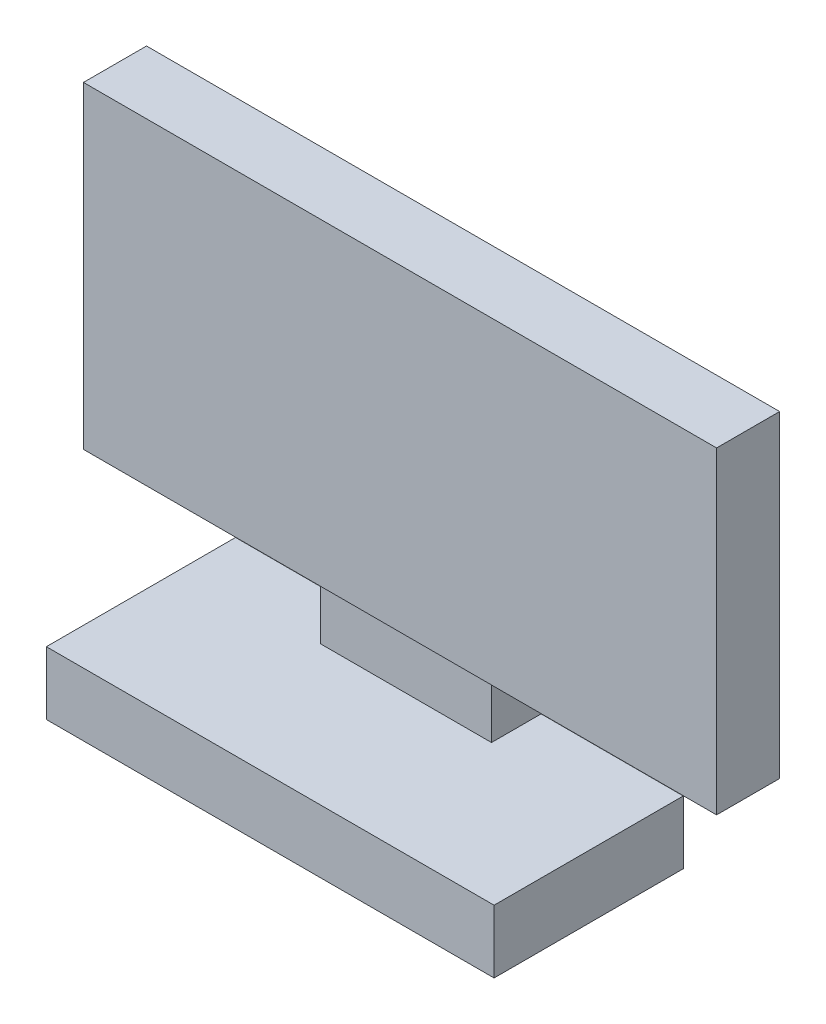
SolidWorks part; units mm, degrees
ref_plane "Front Plane" through (0, 0, 0) normal (0, 0, 1) x (1, 0, 0)
ref_plane "Top Plane" through (0, 0, 0) normal (0, 1, 0) x (1, 0, 0)
ref_plane "Right Plane" through (0, 0, 0) normal (1, 0, 0) x (0, 0, -1)
sketch "Sketch1" plane through (0, 0, 0) normal (0, 1, 0) x (1, 0, 0)
  line L0 (14.5041, 9.9599) -> (50.0041, 9.9599)
  line L5 (14.5041, 21.2754) -> (50.0041, 21.2754)
  line L10 (14.5041, 21.2754) -> (14.5041, 6.2754)
  line L11 (14.5041, 6.2754) -> (50.0041, 6.2754)
  line L12 (50.0041, 21.2754) -> (50.0041, 6.2754)
  line L13 (14.5041, 14.0701) -> (50.0041, 14.1179)
  dimension "D1" = 35.5
  dimension "D2" = 15
extrude "Boss-Extrude7" add sketch "Sketch1" along normal blind 5 contours L13 L12 L5 L10 | L13 L10 L0 L12 | L0 L10 L11 L12 region at (32.2883, 0, -12.0269) region at (32.2541, 0, -8.1176) region at (32.2344, 0, -17.6847)
sketch "Sketch5" plane through (0, 5, 0) normal (0, 1, 0) x (1, 0, 0)
  line L0 (14.5041, 21.2754) -> (50.0041, 21.2754) construction
  line L1 (25.1665, 21.2754) -> (38.7336, 21.2754)
  line L2 (25.1665, 21.2754) -> (25.1665, 17.3426)
  line L3 (25.1665, 17.3426) -> (38.7336, 17.3426)
  line L4 (38.7336, 21.2754) -> (38.7336, 17.3426)
extrude "Boss-Extrude8" add sketch "Sketch5" along normal blind 5
sketch "Sketch6" plane through (1.1246, 10, 0) normal (0, 1, 0) x (1, 0, 0)
  line L2 (6.3022, 21.2948) -> (56.5022, 21.2948)
  line L3 (6.3022, 21.2948) -> (6.3022, 16.2948)
  line L4 (6.3022, 16.2948) -> (56.5022, 16.2948)
  line L5 (56.5022, 21.2948) -> (56.5022, 16.2948)
  dimension "D1" = 50.2
  dimension "D2" = 5
extrude "Boss-Extrude9" add sketch "Sketch6" along normal blind 25.2 contours L3 L2 L5 L4
